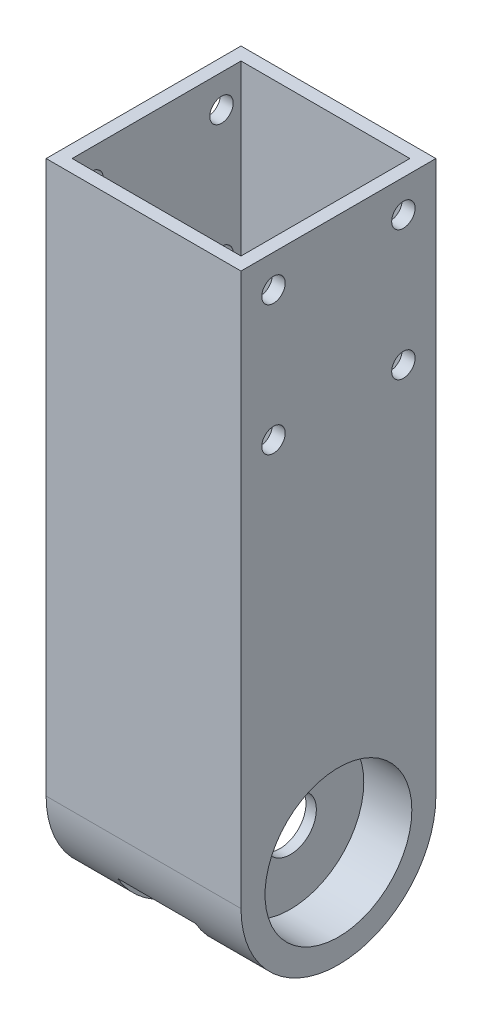
SolidWorks part; units mm, degrees
material "PLA 15%"
ref_plane "Front Plane" through (0, 0, 0) normal (0, 0, 1) x (1, 0, 0)
ref_plane "Top Plane" through (0, 0, 0) normal (0, 1, 0) x (1, 0, 0)
ref_plane "Right Plane" through (0, 0, 0) normal (1, 0, 0) x (0, 0, -1)
sketch "Sketch1" plane through (0, 0, 0) normal (0, 1, 0) x (1, 0, 0)
  line L1 (-15, -15) -> (15, -15)
  line L2 (-15, -15) -> (-15, 15)
  line L3 (-15, 15) -> (15, 15)
  line L4 (15, -15) -> (15, 15)
  line L5 (-15, -15) -> (15, 15) construction
  line L6 (-15, 15) -> (15, -15) construction
  line L11 (-6, -6) -> (6, 6) construction
  line L12 (-6, 6) -> (6, -6) construction
  line L13 (-6, -13) -> (6, -13)
  line L14 (-6, -13) -> (-6, 13)
  line L15 (-6, 13) -> (6, 13)
  line L16 (6, -13) -> (6, 13)
  line L17 (-6, -13) -> (6, 13) construction
  line L18 (-6, 13) -> (6, -13) construction
  point P0 (0, 0)
  point P6 (0, 0)
  point P11 (0, 0)
  dimension "D1" = 30
  dimension "D2" = 30
  dimension "D3" = 9
  dimension "D4" = 2
extrude "Boss-Extrude2" add sketch "Sketch1" along normal blind 100
sketch "Sketch2" plane through (15, 0, 0) normal (1, 0, 0) x (0, 0, -1)
  line L0 (-15, 95) -> (15, 95)
  line L1 (-15, 100) -> (-15, 0) construction
  line L2 (15, 100) -> (15, 0) construction
  line L3 (-15, 100) -> (15, 100) construction
  line L4 (-15, 100) -> (-15, 70) construction
  line L5 (-15, 70) -> (15, 70) construction
  line L6 (-15, 70) -> (15, 70)
  line L8 (-12, 93) -> (-8, 93)
  line L9 (-12, 93) -> (-12, 97)
  line L10 (-12, 97) -> (-8, 97)
  line L11 (-8, 93) -> (-8, 97)
  line L12 (-12, 93) -> (-8, 97) construction
  line L13 (-12, 97) -> (-8, 93) construction
  line L14 (12, 97) -> (8, 97)
  line L15 (12, 97) -> (12, 93)
  line L16 (12, 93) -> (8, 93)
  line L17 (8, 97) -> (8, 93)
  line L18 (12, 97) -> (8, 93) construction
  line L19 (12, 93) -> (8, 97) construction
  line L20 (-12, 73) -> (-8, 73)
  line L21 (-12, 73) -> (-12, 77)
  line L22 (-12, 77) -> (-8, 77)
  line L23 (-8, 73) -> (-8, 77)
  line L24 (-12, 73) -> (-8, 77) construction
  line L25 (-12, 77) -> (-8, 73) construction
  line L26 (8, 73) -> (12, 73)
  line L27 (8, 73) -> (8, 77)
  line L28 (8, 77) -> (12, 77)
  line L29 (12, 73) -> (12, 77)
  line L30 (8, 73) -> (12, 77) construction
  line L31 (8, 77) -> (12, 73) construction
  circle A0 centre (-10, 95) radius 2
  circle A1 centre (10, 95) radius 2
  circle A4 centre (-10, 75) radius 2
  circle A5 centre (10, 75) radius 2
  dimension "D2" = 4
  dimension "D4" = 4
  dimension "D7" = 5
  dimension "D8" = 4
  dimension "D9" = 5
  dimension "D11" = 4
  dimension "D13" = 4
  dimension "D1" = 5
  dimension "D3" = 5
  dimension "D5" = 5
  dimension "D6" = 30
  dimension "D10" = 5
  dimension "D12" = 5
  dimension "D14" = 4
  dimension "D15" = 4
  dimension "D16" = 4
  dimension "D17" = 4
  dimension "D18" = 4
sketch "Sketch3" plane through (0, 100, 0) normal (0, 1, 0) x (1, 0, 0)
  line L0 (-6, 13) -> (-13, 13)
  line L1 (-15, 15) -> (-15, -15) construction
  line L2 (-13, 13) -> (-13, -13)
  line L7 (-6, -13) -> (-13, -13)
  line L8 (-6, 13) -> (-6, -13)
  line L9 (15, -15) -> (15, 15) construction
  line L10 (6, 13) -> (13, 13)
  line L11 (6, 13) -> (6, -13)
  line L12 (6, -13) -> (13, -13)
  line L13 (13, 13) -> (13, -13)
  dimension "D1" = 2
  dimension "D2" = 2
extrude "Cut-Extrude2" cut sketch "Sketch3" against normal blind 70
fillet "Fillet1" radius 15 2 edges at (0, 0, -15) (0, 0, 15)
sketch "Sketch5" plane through (15, 0, 0) normal (1, 0, 0) x (0, 0, -1)
  circle A0 centre (0, 15) radius 4
  dimension "D1" = 8
extrude "Cut-Extrude3" cut sketch "Sketch5" against normal blind 50
sketch "Sketch6" plane through (15, 0, 0) normal (1, 0, 0) x (0, 0, -1)
  circle A0 centre (0, 15) radius 11.3
  dimension "D1" = 22.6
extrude "Cut-Extrude4" cut sketch "Sketch6" against normal blind 7.4
sketch "Sketch7" plane through (-15, 0, 0) normal (-1, 0, 0) x (0, 0, 1)
  circle A0 centre (0, 15) radius 11.3
  dimension "D1" = 22.6
extrude "Cut-Extrude5" cut sketch "Sketch7" against normal blind 7.4
sketch "Sketch8" plane through (15, 0, 0) normal (1, 0, 0) x (0, 0, -1)
  line L3 (10, 75) -> (-10, 75) construction
  line L6 (10, 15) -> (10, 95)
  line L7 (10, 95) -> (-10, 95)
  line L8 (-10, 95) -> (-10, 15)
  line L9 (10, 75) -> (10, 95) construction
  line L10 (10, 95) -> (-10, 95) construction
  line L11 (-10, 95) -> (-10, 75) construction
  arc A4 (-10, 15) -> (0, 5) centre (0, 15) ccw
  arc A5 (0, 5) -> (10, 15) centre (0, 15) ccw
  point P13 (-10, 75)
  point P18 (10, 75)
  point P19 (10, 95)
  point P20 (-10, 95)
  dimension "D1" = 5
hole_wizard "M3 Clearance Hole1" positions "Sketch8" profile "Sketch9" hole size "M3" standard "ANSI Metric" end condition through all
sketch "Sketch9" plane through (15, 95, 10) normal (0, 1, 0) x (0, 0, -1)
  line L0 (0, 0) -> (0, 30)
  line L1 (0, 30) -> (1.8, 30)
  line L2 (1.8, 30) -> (1.8, 0)
  line L5 (1.8, 0) -> (0, 0)
  line L11 (0, -6.35) -> (0, 107.95) construction
  dimension "Thru Hole Dia." = 3.6
  dimension "Thru Hole Depth" = 30
